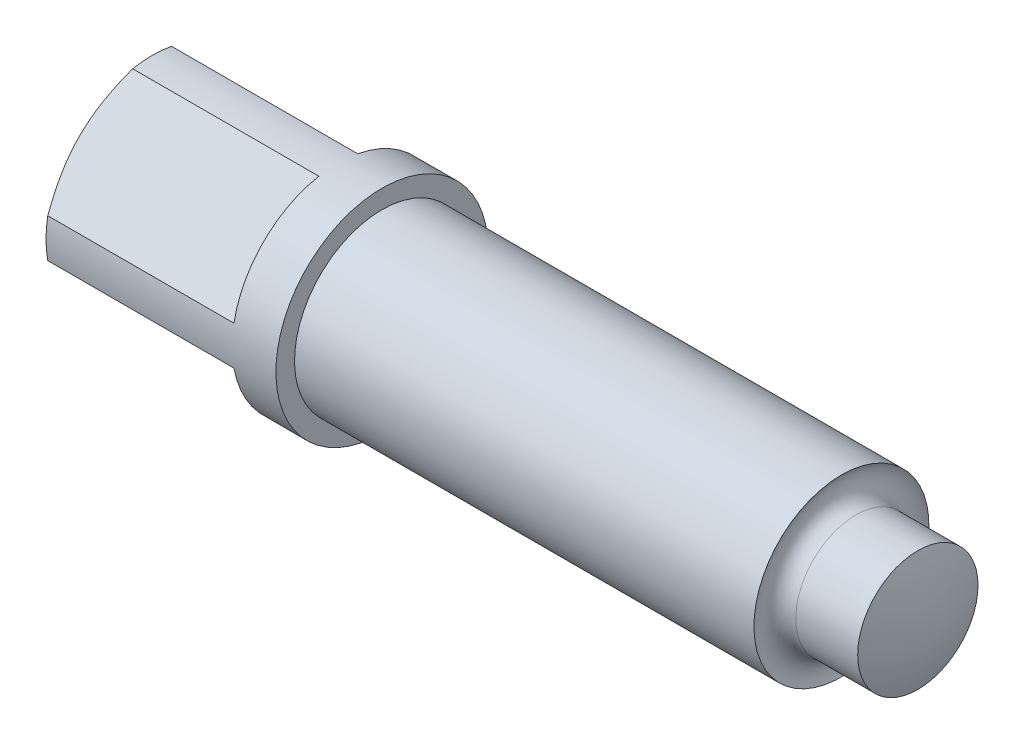
SolidWorks part; units mm, degrees
ref_plane "Front" through (0, 0, 0) normal (0, 0, 1) x (1, 0, 0)
ref_plane "Top" through (0, 0, 0) normal (0, 1, 0) x (1, 0, 0)
ref_plane "Right" through (0, 0, 0) normal (1, 0, 0) x (0, 0, -1)
sketch "Sketch1" plane through (0, 0, 0) normal (1, 0, 0) x (0, 0, -1)
  circle A0 centre (0, 0) radius 4.85
extrude "BaseHead" add sketch "Sketch1" along normal blind 11
sketch "Sketch2" plane through (0, -0.4747, 1.6499) normal (-1, 0, 0) x (0, 0, 1)
  line L1 (4.007, 0.4747) -> (-1.6499, 6.1315)
  line L2 (-1.6499, 6.1315) -> (-7.3067, 0.4747)
  line L3 (-7.3067, 0.4747) -> (-1.6499, -5.1822)
  line L4 (-1.6499, -5.1822) -> (4.007, 0.4747)
  circle A0 centre (-1.6499, 0.4747) radius 4 construction
extrude "Cut-Extrude1" cut sketch "Sketch2" against normal blind 9 flip side to cut
sketch "Sketch3" plane through (2.6897, -8.0247, 0) normal (0, 0, 1) x (0, -1, 0)
  line L0 (-13.3597, -2.6897) -> (-12.0247, -2.6897)
  line L2 (-12.0247, -2.6897) -> (-13.3597, -1.919)
  line L3 (-13.3597, -1.919) -> (-13.3597, -2.6897)
  line L4 (-8.0247, 0.2856) -> (-8.0247, -6.82) construction
  line L6 (-7.1357, -2.6897) -> (-3.2569, -2.6897) construction
  dimension "D1" = 10.67
revolve "Cut-Revolve1" cut sketch "Sketch3" angle 360 about L4
sketch "Sketch4" plane through (-9.8802, 13.8802, 0) normal (0, 0, 1) x (0, -1, 0)
  line L0 (13.8802, 20.8802) -> (17.8802, 20.8802)
  line L1 (17.8802, 24.6302) -> (13.8802, 24.6302) construction
  line L2 (17.8802, 20.8802) -> (17.8802, 41.8802)
  line L3 (18.7302, 20.8802) -> (9.0302, 20.8802) construction
  line L4 (16.6302, 42.5416) -> (16.6302, 45.3724)
  line L5 (13.8802, 45.8802) -> (13.8802, 20.8802)
  line L6 (13.8802, 12.6966) -> (13.8802, -1.2396) construction
  arc A0 (16.6302, 45.3724) -> (13.8802, 45.8802) centre (13.8802, 38.1802) ccw
  arc A1 (16.6302, 42.5416) -> (17.8802, 41.8802) centre (17.4302, 42.5416) ccw
  dimension "re" = 7.7
  dimension "D2" = 0.8
revolve "BaseBody" add sketch "Sketch4" angle 360 about L6
cosmetic thread "ThreadCosmetic1" [suppressed] parameters "D1"=17.25, "D"=6
fillet "HeadFillet" [suppressed] radius 0.4
sketch "Sketch5" plane through (0, 0, 0) normal (0, 0, 1) x (1, 0, 0)
  line L0 (32, 3.134) -> (32.5, 4)
  line L1 (32.5, 4) -> (32.5, 5)
  line L2 (32.5, 5) -> (31.5, 5)
  line L3 (31.5, 5) -> (31.5, 4)
  line L4 (31.5, 4) -> (32, 3.134)
  line L5 (32, 4) -> (32, -4) construction
  line L6 (0, 0) -> (37.4265, 0) construction
  dimension "D1" = 8
  dimension "D2" = 1
revolve "Cut-Revolve10" [suppressed] cut sketch "Sketch5" angle 360 about L6
pattern_linear "LPattern10" [suppressed] count 14 spacing 1.2 along (-1, 0, 0) of bodies 106
equation "\"D1@Sketch3\" = \"e@Sketch1\" * 1.1"
equation "\"d2@Sketch3\" = \"s@Sketch2\""
equation "\"D2@Sketch4\" = \"r@HeadFillet\" * 2"
equation "\"D1@ThreadCosmetic1\" = \"l@Sketch4\" - \"a@Sketch4\" - \"z@Sketch4\""
equation "\"D1@Sketch5\" = \"d@Sketch4\""
equation "\"D2@Sketch5\" =  ( \"d@Sketch4\" - \"D@ThreadCosmetic1\" )  / 2"
equation "\"D3@LPattern10\" = \"D2@Sketch5\" * 1.2"
equation "\"D1@LPattern10\" = \"D1@ThreadCosmetic1\" / \"D3@LPattern10\""
